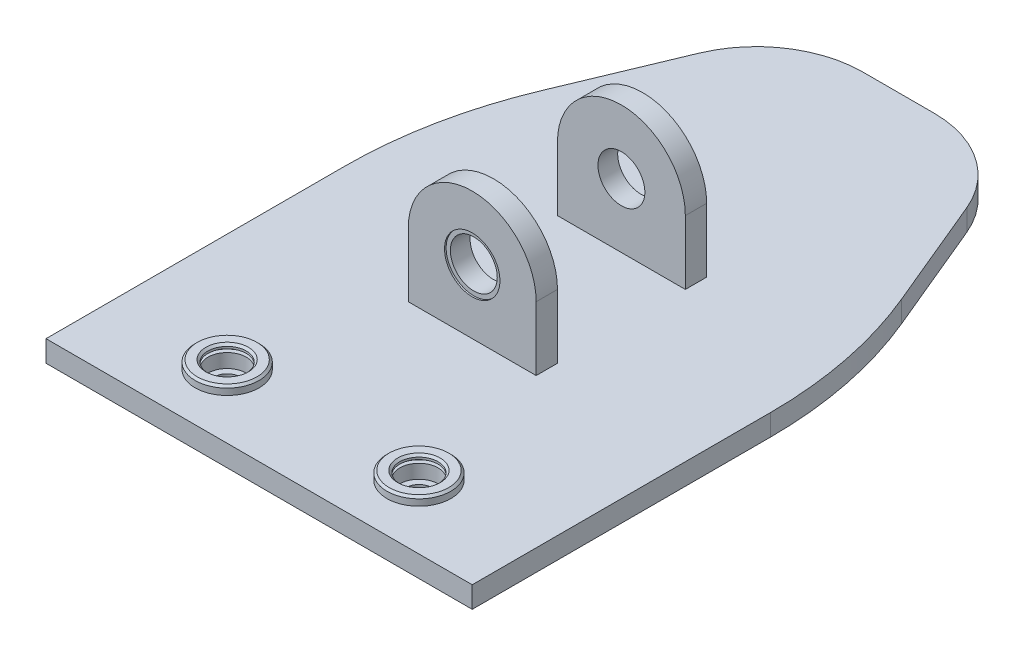
SolidWorks part; units mm, degrees
ref_plane "前视基准面" through (0, 0, 0) normal (0, 0, 1) x (1, 0, 0)
ref_plane "上视基准面" through (0, 0, 0) normal (0, 1, 0) x (1, 0, 0)
ref_plane "右视基准面" through (0, 0, 0) normal (1, 0, 0) x (0, 0, -1)
other "Configuration Table"
sketch "草图1" plane through (0, 0, 0) normal (0, 1, 0) x (1, 0, 0)
  line L0 (0, 0) -> (0, 255.8207) construction
  line L1 (-100, 0) -> (100, 0)
  line L2 (100, 0) -> (100, 180)
  line L3 (100, 180) -> (50, 300)
  line L4 (50, 300) -> (-50, 300)
  line L5 (-100, 180) -> (-50, 300)
  line L6 (-100, 0) -> (-100, 180)
  point P8 (0, 300)
  dimension "D1" = 300
  dimension "D2" = 100
  dimension "D3" = 120
  dimension "D4" = 50
extrude "凸台-拉伸1" add sketch "草图1" along normal blind 10
sketch "草图2" plane through (100, 0, 0) normal (1, 0, 0) x (0, 0, -1)
  line L0 (40, 100) -> (40, -10.3339) construction
  line L1 (0, 10) -> (0, 0) construction
  line L2 (0, 10) -> (0, 60)
  line L3 (80, 10) -> (80, 60)
  arc A0 (80, 60) -> (0, 60) centre (40, 60) ccw
  circle A1 centre (40, 60) radius 10
  line M6 (180, 10) -> (0, 10)
  dimension "D3" = 20
  dimension "D1" = 40
  dimension "D2" = 50
extrude "凸台-拉伸2" [suppressed] add sketch "草图2" against normal up to surface (200 mm away) contours A0 L0 A1 L3 M6 | L0 A0 L2 A1 M6 up to face at (-100, 5, -90)
sketch "草图3" [suppressed] plane through (0, 10, 0) normal (0, 1, 0) x (1, 0, 0)
  line L0 (0, 0) -> (0, 135.8056) construction
  line L1 (-100, 0) -> (100, 0) construction
  line L2 (-70, 0) -> (70, 0)
  line L3 (-70, 0) -> (-70, 100)
  line L4 (-70, 100) -> (70, 100)
  line L5 (70, 0) -> (70, 100)
  line L6 (100, 0) -> (100, 80) construction
  line L7 (-100, 80) -> (-100, 0) construction
  dimension "D1" = 30
  dimension "D2" = 30
  dimension "D3" = 100
extrude "切除-拉伸1" [suppressed] cut sketch "草图3" along normal blind 171
sketch "草图4" plane through (0, 0, 0) normal (0, 0, 1) x (1, 0, 0)
  line L0 (0, 0) -> (0, 92.3322) construction
  line L1 (30, 40) -> (30, 10)
  line L2 (-30, 40) -> (-30, 10)
  line L3 (-100, 10) -> (100, 10) construction
  arc A0 (-30, 40) -> (30, 40) centre (0, 40) cw
  circle A1 centre (0, 40) radius 11
  line M10 (100, 10) -> (-100, 10)
  dimension "D2" = 30
  dimension "D3" = 22
  dimension "D1" = 30
extrude "凸台-拉伸3" add sketch "草图4" against normal blind 80 from offset 100 contours L0 L1 A0 A1 M10 | L0 A1 A0 L2 M10 region at (-15.2547, 36.8238, 0) region at (15.2547, 36.8238, 0) offset against normal yes
sketch "草图5" plane through (0, 10, 0) normal (0, 1, 0) x (1, 0, 0)
  line L0 (-47.074, 140) -> (51.1394, 140) construction
  line L1 (30, 180) -> (-30, 180) construction
  line L2 (30, 100) -> (-30, 100) construction
  line L3 (-30, 100) -> (30, 100) construction
  line L4 (-40, 170) -> (40, 170)
  line L5 (-40, 170) -> (-40, 110)
  line L6 (-40, 110) -> (40, 110)
  line L7 (40, 170) -> (40, 110)
  line L8 (30, 180) -> (30, 100) construction
  line L9 (-30, 180) -> (-30, 100) construction
  dimension "D1" = 10
  dimension "D2" = 10
  dimension "D3" = 10
  dimension "D4" = 10
extrude "切除-拉伸2" cut sketch "草图5" along normal blind 110 contours L7 L6 L5 L4
fillet "圆角1" radius 50 2 edges at (-50, 5, -300) (50, 5, -300)
fillet "圆角2" radius 200 2 edges at (-100, 5, -180) (100, 5, -180)
sketch "草图6" [suppressed] plane through (100, 0, 0) normal (1, 0, 0) x (0, 0, -1)
  line L0 (40, 60) -> (40, -52.2503) construction
  circle A0 centre (40, 60) radius 10 construction
  circle A1 centre (40, 60) radius 10 construction
  arc A2 (73.0468, 82.5368) -> (6.9532, 82.5368) centre (40, -25) ccw
  arc A3 (80, 60) -> (0, 60) centre (40, 60) ccw construction
  arc A4 (73.0468, 82.5368) -> (6.9532, 82.5368) centre (40, 60) ccw
  dimension "D2" = 225
  dimension "D1" = 25
extrude "切除-拉伸3" [suppressed] cut sketch "草图6" against normal through all both and the other way through all contours A2 A4
sketch "草图7" plane through (0, 10, 0) normal (0, 1, 0) x (1, 0, 0)
  line L0 (0, 0) -> (0, 141.3983) construction
  line L1 (-100, 0) -> (100, 0) construction
  circle A0 centre (45, 30) radius 9
  dimension "D1" = 18
  dimension "D2" = 45
  dimension "D3" = 30
extrude "切除-拉伸6" cut sketch "草图7" against normal offset from surface (6 mm away) 4 contours A0 up to face at (0, 0, -186.7805)
sketch "草图10" plane through (0, 4, 0) normal (0, 1, 0) x (1, 0, 0)
  circle A0 centre (45, 30) radius 6
  dimension "D1" = 12
extrude "切除-拉伸7" cut sketch "草图10" against normal blind 28 contours A0
sketch "草图11" plane through (0, 10, 0) normal (0, 1, 0) x (1, 0, 0)
  circle A0 centre (45, 30) radius 12.5
  circle A1 centre (45, 30) radius 16.5
  dimension "D1" = 25
  dimension "D2" = 33
extrude "切除-拉伸8" [suppressed] cut sketch "草图11" against normal blind 5
sketch "草图12" plane through (0, 10, 0) normal (0, 1, 0) x (1, 0, 0)
  circle A0 centre (45, 30) radius 15
  dimension "D1" = 30
extrude "凸台-拉伸5" add sketch "草图12" along normal blind 4 contours A0
sketch "草图13" plane through (0, 14, 0) normal (0, 1, 0) x (1, 0, 0)
  circle A0 centre (45, 30) radius 9
  dimension "D1" = 18
extrude "切除-拉伸9" cut sketch "草图13" against normal blind 4
sketch "草图14" plane through (0, 14, 0) normal (0, 1, 0) x (1, 0, 0)
  circle A0 centre (45, 30) radius 11
  circle A1 centre (45, 30) radius 9 construction
  circle A2 centre (45, 30) radius 9 construction
  circle A3 centre (45, 30) radius 9
  circle M1 centre (45, 30) radius 9
  dimension "D1" = 2
extrude "卡簧槽" cut sketch "草图14" against normal blind 1.5 from offset 2 contours M1 | A0 region at (45, 14, -30) offset against normal yes
chamfer "倒角1" distance 1 angle 45 2 edges at (45, 14, -15) (45, 14, -21)
ref_plane "基准面1" through (0, 0, 0) normal (-1, 0, 0) x (0, 0, 1)
mirror "镜向1" about plane through (0, 0, 0) normal (-1, 0, 0) of "切除-拉伸6", "切除-拉伸7", "凸台-拉伸5", "切除-拉伸9", "卡簧槽", "倒角1"
sketch "草图16" plane through (0, 0, -100) normal (0, 0, 1) x (1, 0, 0)
  circle A0 centre (0, 40) radius 13
  dimension "D1" = 26
extrude "切除-拉伸10" cut sketch "草图16" against normal blind 0.75
sketch "草图17" plane through (0, 0, -180) normal (0, 0, -1) x (-1, 0, 0)
  circle A0 centre (0, 40) radius 13
  dimension "D1" = 26
extrude "切除-拉伸11" cut sketch "草图17" against normal blind 0.75 contours A0
